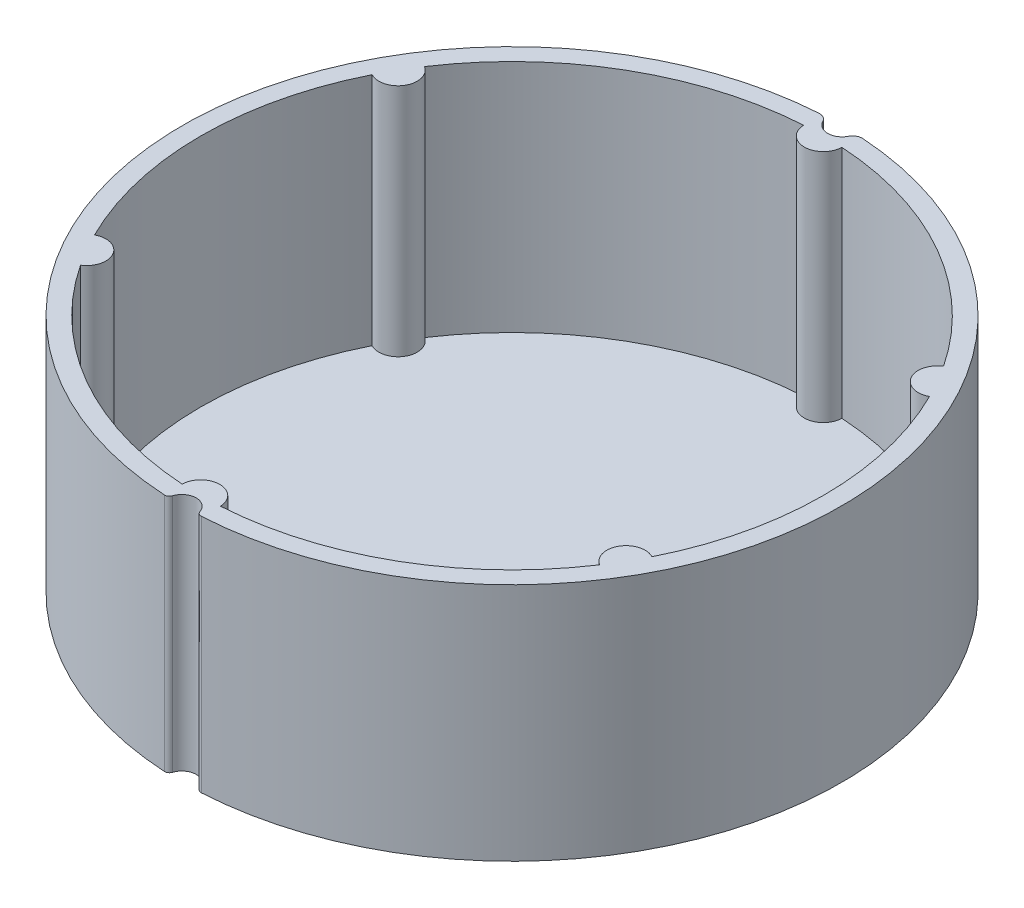
SolidWorks part; units mm, degrees
ref_plane "Front Plane" through (0, 0, 0) normal (0, 0, 1) x (1, 0, 0)
ref_plane "Top Plane" through (0, 0, 0) normal (0, 1, 0) x (1, 0, 0)
ref_plane "Right Plane" through (0, 0, 0) normal (1, 0, 0) x (0, 0, -1)
sketch "Sketch1" plane through (0, 0, 0) normal (0, 1, 0) x (1, 0, 0)
  line L3 (0, 0) -> (0, 3.1872) construction
  line L4 (0, 3.1872) -> (2.417, 3.1872)
  line L5 (0, 3.1872) -> (-2.417, 3.1872)
  line L6 (0, 32.9542) -> (0, 0) construction
  line L7 (0, 0) -> (-0.0105, -32.9541) construction
  arc A0 (1.9225, -34.3462) -> (2.2975, 34.3232) centre (0, 0) ccw
  arc A2 (-2.417, 3.1872) -> (2.417, 3.1872) centre (0, 0) ccw
  circle A3 centre (0, 0) radius 34.4 construction
  arc A7 (-1.3384, 33.7769) -> (1.3384, 33.7769) centre (0, 34.4542) ccw
  arc A9 (-2.2975, 34.3232) -> (-1.9445, -34.345) centre (0, 0) ccw
  arc A11 (1.3384, 33.7769) -> (2.2975, 34.3232) centre (2.2307, 33.3254) cw
  arc A12 (-1.3384, 33.7769) -> (-2.2975, 34.3232) centre (-2.2307, 33.3254) ccw
  arc A13 (1.4182, -33.9988) -> (-1.44, -33.9979) centre (-0.011, -34.4541) ccw
  arc A14 (1.4182, -33.9988) -> (1.9225, -34.3462) centre (1.8946, -33.847) ccw
  arc A15 (-1.44, -33.9979) -> (-1.9445, -34.345) centre (-1.9163, -33.8458) cw
  point P15 (1.4997, 33.97)
  dimension "D2" = 4.834
  dimension "D3" = 4
  dimension "D4" = 34.4
  dimension "D5" = 1
  dimension "D6" = 1.5
  dimension "D7" = 0.5
  dimension "D8" = 1.5
  dimension "D9" = 1.9335
  dimension "D11" = 1.4997
sketch "Sketch2" plane through (0, 0, 0) normal (0, 1, 0) x (1, 0, 0)
  line L0 (0, 32.5) -> (0, 30.5) construction
  line L1 (28.1458, 16.25) -> (26.4138, 15.25) construction
  line L2 (28.1458, -16.25) -> (26.4138, -15.25) construction
  line L3 (0, -32.5) -> (0, -30.5) construction
  line L4 (-28.1458, -16.25) -> (-26.4138, -15.25) construction
  line L5 (-28.1458, 16.25) -> (-26.4138, 15.25) construction
  arc A16 (-1.9991, 32.4385) -> (-28.1458, 16.25) centre (0, 0) ccw
  arc A17 (1.9991, 32.4385) -> (-1.9991, 32.4385) centre (0, 32.5) cw
  arc A18 (29.0921, 14.488) -> (27.093, 17.9505) centre (28.1458, 16.25) cw
  arc A19 (27.093, -17.9505) -> (29.0921, -14.488) centre (28.1458, -16.25) cw
  arc A20 (-1.9991, -32.4385) -> (1.9991, -32.4385) centre (0, -32.5) cw
  arc A21 (-29.0921, -14.488) -> (-27.093, -17.9505) centre (-28.1458, -16.25) cw
  arc A22 (-27.093, 17.9505) -> (-29.0921, 14.488) centre (-28.1458, 16.25) cw
  arc A23 (27.093, 17.9505) -> (0, 32.5) centre (0, 0) ccw
  arc A24 (29.0921, -14.488) -> (28.1458, 16.25) centre (0, 0) ccw
  arc A25 (0, -32.5) -> (28.1458, -16.25) centre (0, 0) ccw
  arc A26 (-27.093, -17.9505) -> (-1.9991, -32.4385) centre (0, 0) ccw
  arc A27 (-29.0921, 14.488) -> (-28.1458, -16.25) centre (0, 0) ccw
  point P29 (0, 0)
  dimension "D1" = 65
  dimension "D2" = 2
  dimension "D3" = 6
extrude "Boss-Extrude1" add sketch "Sketch1" along normal blind 25 contours A0 A7 A9 A2 L5 L4 region at (2.1624, 0, 33.4583)
extrude "Cut-Extrude2" cut sketch "Sketch2" along normal through all contours A22 A27 A21 A26 A20 A25 A19 A24 A18 A23 A17 A16 region at (0, 0, 0)
extrude "Boss-Extrude2" add sketch "Sketch2<2>" along normal blind 0.5 contours A22 A27 A21 A26 A20 A25 A19 A24 A18 A23 A17 A16 region at (0, 0, 0)
sketch "Sketch2<2>" plane through (0, 0, 0) normal (0, 1, 0) x (1, 0, 0) same geometry as "Sketch2"
